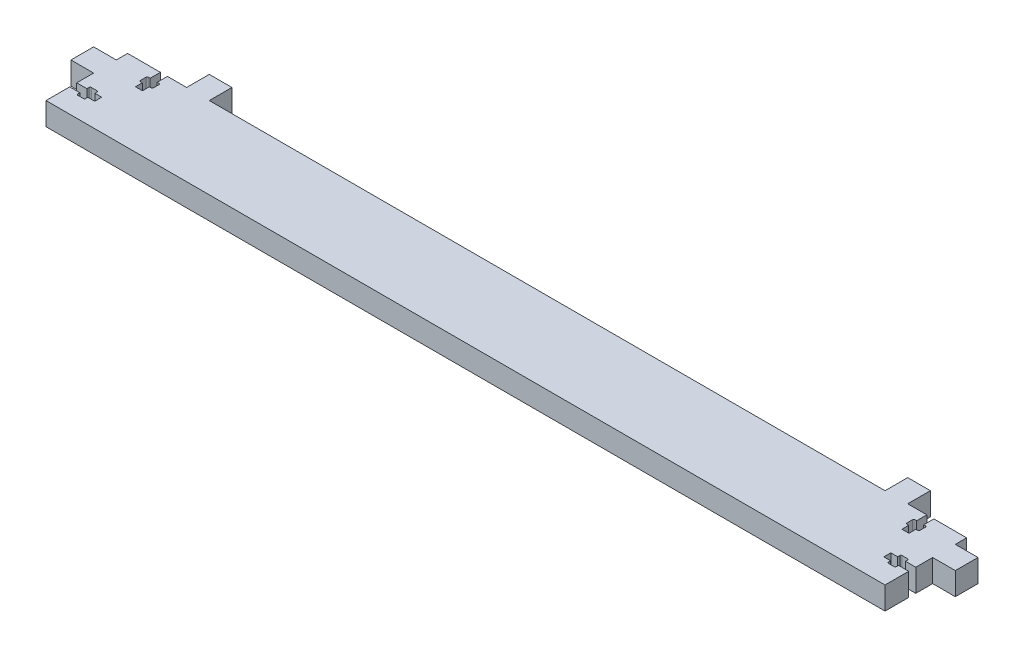
SolidWorks part; units mm, degrees
ref_plane "Front Plane" through (0, 0, 0) normal (0, 0, 1) x (1, 0, 0)
ref_plane "Top Plane" through (0, 0, 0) normal (0, 1, 0) x (1, 0, 0)
ref_plane "Right Plane" through (0, 0, 0) normal (1, 0, 0) x (0, 0, -1)
sketch "Sketch1" plane through (0, 0, 0) normal (0, 1, 0) x (1, 0, 0)
  line L0 (0, 18) -> (0, -18) construction
  line L1 (-185, 18) -> (0, 18)
  line L2 (-185, 18) -> (-185, 13)
  line L3 (-185, -18) -> (0, -18)
  line L4 (0, 18) -> (0, -18)
  line L5 (-185, 18) -> (0, 0) construction
  line L6 (-185, -18) -> (0, 0) construction
  line L7 (-185, 13) -> (-195, 13)
  line L8 (-195, 13) -> (-195, 3)
  line L9 (-195, 3) -> (-185, 3)
  line L10 (-185, 3) -> (-185, -18)
  point P0 (0, 0)
  dimension "D6" = 10
  dimension "D7" = 10
  dimension "D1" = 185
  dimension "D2" = 36
  dimension "D4" = 5
  dimension "D9" = 18
extrude "MainShape" add sketch "Sketch1" along normal blind 10 contours L2 L7 L8 L9 region at (-93.9423, 0, -0.1183)
sketch "Sketch2" plane through (0, 10, 0) normal (0, 1, 0) x (1, 0, 0)
  line L0 (-169, 18) -> (-169, 7) construction
  line L1 (-185, 18) -> (0, 18) construction
  line L2 (-170.55, 18) -> (-170.55, 13.5)
  line L3 (-170.55, 13.5) -> (-171.35, 13.5)
  line L4 (-171.85, 13) -> (-171.85, 10.5)
  line L5 (-171.35, 10) -> (-170.55, 10)
  line L6 (-170.55, 10) -> (-170.55, 7)
  line L7 (-170.55, 7) -> (-167.45, 7)
  line L8 (-185, 18) -> (-185, 13) construction
  line L9 (-170.55, 18) -> (-167.45, 18)
  line L10 (-167.45, 10) -> (-167.45, 7)
  line L11 (-166.65, 10) -> (-167.45, 10)
  line L12 (-166.15, 13) -> (-166.15, 10.5)
  line L13 (-167.45, 13.5) -> (-166.65, 13.5)
  line L14 (-167.45, 18) -> (-167.45, 13.5)
  line L16 (-185, -6) -> (-174, -6) construction
  line L50 (-185, 3) -> (-185, -18) construction
  line L51 (-174, -7.55) -> (-174, -4.45)
  line L52 (-174, -4.45) -> (-177, -4.45)
  line L53 (-177, -4.45) -> (-177, -3.5)
  line L54 (-177.5, -3) -> (-180, -3)
  line L55 (-180.5, -3.5) -> (-180.5, -4.45)
  line L56 (-180.5, -4.45) -> (-185, -4.45)
  line L57 (-185, -4.45) -> (-185, -7.55)
  line L58 (-195, 13) -> (-195, 3) construction
  line L59 (-180.5, -7.55) -> (-185, -7.55)
  line L60 (-180.5, -8.5) -> (-180.5, -7.55)
  line L61 (-177.5, -9) -> (-180, -9)
  line L62 (-177, -7.55) -> (-177, -8.5)
  line L63 (-174, -7.55) -> (-177, -7.55)
  arc A0 (-171.85, 10.5) -> (-171.35, 10) centre (-171.35, 10.5) ccw
  arc A1 (-171.35, 13.5) -> (-171.85, 13) centre (-171.35, 13) ccw
  arc A2 (-166.65, 13.5) -> (-166.15, 13) centre (-166.65, 13) cw
  arc A3 (-166.15, 10.5) -> (-166.65, 10) centre (-166.65, 10.5) cw
  arc A16 (-177, -3.5) -> (-177.5, -3) centre (-177.5, -3.5) ccw
  arc A17 (-180, -3) -> (-180.5, -3.5) centre (-180, -3.5) ccw
  arc A18 (-180, -9) -> (-180.5, -8.5) centre (-180, -8.5) cw
  arc A19 (-177, -8.5) -> (-177.5, -9) centre (-177.5, -8.5) cw
  point P14 (-171.85, 10)
  point P17 (-171.85, 13.5)
  point P28 (-166.15, 13.5)
  point P29 (-166.15, 10)
  point P34 (-195, 8)
  point P45 (-177, -3)
  point P48 (-180.5, -3)
  dimension "D8" = 0.5
  dimension "D16" = 0.5
  dimension "D1" = 11
  dimension "D2" = 1.55
  dimension "D3" = 1.55
  dimension "D4" = 8
  dimension "D5" = 2.85
  dimension "D6" = 3.5
  dimension "D7" = 16
  dimension "D9" = 11
  dimension "D10" = 8
  dimension "D11" = 3.5
  dimension "D12" = 3
  dimension "D13" = 1.55
  dimension "D14" = 1.55
  dimension "D15" = 14
extrude "ScrewSlots" cut sketch "Sketch2" against normal through all
mirror "Mirror1" about plane through (0, 0, 0) normal (1, 0, 0) of "ScrewSlots", "MainShape"
sketch "Sketch6" [suppressed] plane through (0, 10, 0) normal (0, 1, 0) x (1, 0, 0)
  line L0 (0, -18) -> (0, -48) construction
  line L2 (-185, -18) -> (185, -18) construction
  line L3 (90, -48) -> (-90, -48)
  line L4 (-90, -48) -> (-120, -18)
  line L5 (90, -48) -> (120, -18)
  line L6 (-120, -18) -> (120, -18)
  dimension "D1" = 135
  dimension "D2" = 30
  dimension "D3" = 90
extrude "Boss-Extrude1" [suppressed] add sketch "Sketch6" against normal through all
sketch "Sketch8" [suppressed] plane through (0, 10, 0) normal (0, 1, 0) x (1, 0, 0)
  line L0 (-71.5, 4.8833) -> (-77.5, 4.8833) construction
  line L1 (-77, -1.6167) -> (-72, -1.6167)
  line L2 (-78, -0.6167) -> (-78, 4.3833)
  line L3 (-77, 5.3833) -> (-72, 5.3833)
  line L4 (-71, -0.6167) -> (-71, 4.3833)
  line L5 (-78, -1.6167) -> (-71, 5.3833) construction
  line L6 (-78, 5.3833) -> (-71, -1.6167) construction
  line L7 (-71.5, -1.1167) -> (-71.5, 4.8833) construction
  circle A0 centre (-74.5, -34.7667) radius 6.5
  circle A1 centre (-74.5, -15.8167) radius 5.5
  arc A2 (-77, -1.6167) -> (-78, -0.6167) centre (-77, -0.6167) cw
  circle A3 centre (-74.5, -34.7667) radius 6 construction
  circle A4 centre (-74.5, -15.8167) radius 3.5 construction
  arc A5 (-72, -1.6167) -> (-71, -0.6167) centre (-72, -0.6167) ccw
  arc A6 (-72, 5.3833) -> (-71, 4.3833) centre (-72, 4.3833) cw
  arc A7 (-78, 4.3833) -> (-77, 5.3833) centre (-77, 4.3833) cw
  point P6 (-74.5, 1.8833)
  dimension "D1" = 0.5
  dimension "D2" = 2
  dimension "D3" = 0.5
  dimension "D5" = 1
  dimension "D4" = 0.5
extrude "Cut-Extrude2" [suppressed] cut sketch "Sketch8" against normal through all
sketch "Sketch7" [suppressed] plane through (0, 10, 0) normal (0, 1, 0) x (1, 0, 0)
  circle A0 centre (60.5, -43.0167) radius 1.45
  circle A1 centre (-84.5, -43.0167) radius 1.45
  circle A2 centre (-84.5, 6.4833) radius 1.45
  circle A3 centre (60.5, 6.4833) radius 1.45
  dimension "D1" = 2.9
  dimension "D2" = 2.9
  dimension "D3" = 2.9
  dimension "D4" = 2.9
extrude "Cut-Extrude1" [suppressed] cut sketch "Sketch7" against normal through all
sketch "Sketch9" [suppressed] plane through (0, 10, 0) normal (0, 1, 0) x (1, 0, 0)
  line L0 (0, 7.2333) -> (0, -32.7667) construction
  line L1 (48.5, 7.2333) -> (-48.5, 7.2333) construction
  line L2 (-48.5, -32.7667) -> (48.5, -32.7667) construction
  line L3 (-48.5, -12.7667) -> (48.5, -12.7667) construction
  line L4 (-48.5, 7.2333) -> (-48.5, -32.7667) construction
  line L5 (48.5, -32.7667) -> (48.5, 7.2333) construction
  line L7 (-49, -33.2667) -> (49, -33.2667)
  line L8 (-49, -33.2667) -> (-49, 7.7333)
  line L9 (-49, 7.7333) -> (49, 7.7333)
  line L10 (49, -33.2667) -> (49, 7.7333)
  line L11 (-49, -33.2667) -> (49, 7.7333) construction
  line L12 (-49, 7.7333) -> (49, -33.2667) construction
  point P12 (0, -12.7667)
  dimension "D1" = 0.5
  dimension "D2" = 0.5
extrude "Cut-Extrude3" [suppressed] cut sketch "Sketch9" against normal through all and the other way through all
sketch "Sketch10" [suppressed] plane through (0, 10, 0) normal (0, 1, 0) x (1, 0, 0)
  line L0 (20, -39.2667) -> (20, -40.7667) construction
  line L1 (40, -39.2667) -> (0, -39.2667) construction
  line L2 (0, -40.7667) -> (40, -40.7667) construction
  line L3 (0, -40.0167) -> (40, -40.0167) construction
  line L4 (0, -39.2667) -> (0, -40.7667) construction
  line L5 (40, -40.7667) -> (40, -39.2667) construction
  line L7 (-0.2, -40.9667) -> (40.2, -40.9667)
  line L8 (-0.2, -40.9667) -> (-0.2, -39.0667)
  line L9 (-0.2, -39.0667) -> (40.2, -39.0667)
  line L10 (40.2, -40.9667) -> (40.2, -39.0667)
  line L11 (-0.2, -40.9667) -> (40.2, -39.0667) construction
  line L12 (-0.2, -39.0667) -> (40.2, -40.9667) construction
  point P12 (20, -40.0167)
  dimension "D1" = 0.2
  dimension "D2" = 0.2
extrude "Cut-Extrude4" [suppressed] cut sketch "Sketch10" against normal through all
sketch "Sketch12" [suppressed] plane through (0, 0, 0) normal (0, -1, 0) x (-1, 0, 0)
  line L1 (81.4, -9.8167) -> (67.6, -9.8167)
  line L2 (81.4, -9.8167) -> (81.4, -21.8167)
  line L3 (81.4, -21.8167) -> (67.6, -21.8167)
  line L4 (67.6, -9.8167) -> (67.6, -21.8167)
  line L5 (81.4, -9.8167) -> (67.6, -21.8167) construction
  line L6 (81.4, -21.8167) -> (67.6, -9.8167) construction
  point P0 (74.5, -15.8167)
  dimension "D1" = 13.8
  dimension "D2" = 12
extrude "PotentiometerAdjustment" [suppressed] cut sketch "Sketch12" against normal through all
sketch "Sketch11" plane through (0, 0, 0) normal (0, -1, 0) x (1, 0, 0)
  line L1 (-149, -2) -> (-167, -2)
  line L2 (-147, 0) -> (-147, 7)
  line L3 (-149, 9) -> (-167, 9)
  line L4 (-169, 0) -> (-169, 7)
  line L5 (-147, -2) -> (-169, 9) construction
  line L6 (-147, 9) -> (-169, -2) construction
  line L7 (170.55, -7) -> (167.45, -7) construction
  line L8 (-174, 7.55) -> (-174, 4.45) construction
  arc A0 (-147, 7) -> (-149, 9) centre (-149, 7) ccw
  arc A1 (-167, 9) -> (-169, 7) centre (-167, 7) ccw
  arc A2 (-167, -2) -> (-169, 0) centre (-167, 0) cw
  arc A3 (-149, -2) -> (-147, 0) centre (-149, 0) ccw
  point P0 (-158, 3.5)
  dimension "D3" = 2
  dimension "D1" = 22
  dimension "D2" = 11
  dimension "D4" = 5
  dimension "D5" = 5
extrude "LCDCableCutout" [suppressed] cut sketch "Sketch11" against normal through all
sketch "Sketch13" plane through (0, 10, 0) normal (0, 1, 0) x (1, 0, 0)
  line L0 (0, 18) -> (0, -18) construction
  line L1 (-167.45, 18) -> (167.45, 18) construction
  line L2 (-185, -18) -> (185, -18) construction
  line L3 (120, 18) -> (-120, 18) construction
  line L4 (120, 8) -> (-120, 8)
  line L5 (120, 28) -> (-120, 28)
  arc A0 (120, 8) -> (120, 28) centre (120, 18) ccw
  arc A1 (-120, 28) -> (-120, 8) centre (-120, 18) ccw
  point P8 (0, 18)
  dimension "D2" = 120
  dimension "D1" = 10
extrude "Cut-Extrude5" [suppressed] cut sketch "Sketch13" against normal through all
sketch "Sketch14" plane through (0, 10, 0) normal (0, 1, 0) x (1, 0, 0)
  line L1 (-167.45, 18) -> (167.45, 18) construction
  line L3 (-154, 18) -> (-154, 28) construction
  line L4 (-159, 18) -> (-149, 18)
  line L5 (-159, 18) -> (-159, 28)
  line L6 (-159, 28) -> (-149, 28)
  line L7 (-149, 18) -> (-149, 28)
  line L8 (-170.55, 7) -> (-167.45, 7) construction
  line L9 (154, 18) -> (154, 28) construction
  line L10 (149, 18) -> (149, 28)
  line L11 (159, 28) -> (149, 28)
  line L12 (159, 18) -> (159, 28)
  line L13 (159, 18) -> (149, 18)
  point P12 (-169, 7)
  dimension "D1" = 10
  dimension "D2" = 10
  dimension "D3" = 15
extrude "Boss-Extrude3" add sketch "Sketch14" against normal through all
equation "\"Y-ROD-SPACING\"=75"
equation "\"Y-BED-OFFSET\"=2"
equation "\"Y-BED-ROD-INSET\"=3.5"
equation "\"T-SLOT-NUT-FILLET-RADIUS\"=0.5"
equation "\"T-SLOT-SCREW-SHAFT-RADIUS\"=1.55"
equation "\"T-SLOT-SCREW-SHAFT-CUTOUT-LENGTH\"=11.0"
equation "\"T-SLOT-NUT-DEPTH\"=3.5"
equation "\"T-SLOT-NUT-WIDTH\"=2.85"
equation "\"T-SLOT-NUT-END-DISTANCE\"=8"
equation "\"ACRYLIC-TAB-CUTOUT-SIZE\"=\"ACRYLIC-THICKNESS\"+\"ACRYLIC-TAB-TOLERANCE\"*2"
equation "\"ACRYLIC-M3-HOLE\"=2.9"
equation "\"SMOOTHROD-CAP-SCREW-DISTANCE\"=20"
equation "\"D2@Sketch2\"=\"T-SLOT-SCREW-SHAFT-RADIUS\""
equation "\"D1@Sketch2\"=\"T-SLOT-SCREW-SHAFT-CUTOUT-LENGTH\""
equation "\"D6@Sketch2\"=\"T-SLOT-NUT-DEPTH\""
equation "\"D5@Sketch2\"=\"T-SLOT-NUT-WIDTH\""
equation "\"D3@Sketch2\"=\"T-SLOT-SCREW-SHAFT-RADIUS\""
equation "\"D8@Sketch2\"=\"T-SLOT-NUT-FILLET-RADIUS\""
equation "\"D4@Sketch2\"=\"T-SLOT-NUT-END-DISTANCE\""
equation "\"D11@Sketch2\"=\"T-SLOT-NUT-DEPTH\""
equation "\"D10@Sketch2\"=\"T-SLOT-NUT-END-DISTANCE\""
equation "\"D13@Sketch2\"=\"T-SLOT-SCREW-SHAFT-RADIUS\""
equation "\"D14@Sketch2\"=\"T-SLOT-SCREW-SHAFT-RADIUS\""
equation "\"D16@Sketch2\"=\"T-SLOT-NUT-FILLET-RADIUS\""
equation "\"D9@Sketch2\"=\"T-SLOT-SCREW-SHAFT-CUTOUT-LENGTH\""
equation "\"ACRYLIC-TAB-WIDTH\"=\"ACRYLIC-THICKNESS\""
equation "\"D6@Sketch1\"=\"ACRYLIC-TAB-WIDTH\""
equation "\"D7@Sketch1\"=\"ACRYLIC-TAB-WIDTH\""
equation "\"FRAME-WIDTH-INNER\"=370"
equation "\"D1@Sketch1\"=\"FRAME-WIDTH-INNER\"/2"
equation "\"X-ROD-SPACING\"=45"
equation "\"Z-ROD-SPACING\"=17.5"
equation "\"ACRYLIC-THICKNESS\"=10"
equation "\"ACRYLIC-THICKNESS2\"=4.5"
equation "\"NEMA17-HOLE-SPACING\"=31"
equation "\"NEMA17-CENTRAL-CUTOUT\"=22.5"
equation "\"Z-BRACKET-REACH\"=55"
equation "\"TOP-BRACKET-SPACING\"=40"
equation "\"SMOOTHROD-X-LENGTH\"=350"
equation "\"SMOOTHROD-Y-LENGTH\"=350"
equation "\"SMOOTHROD-Z-LENGTH\"=350"
equation "\"SMOOTHROD-TIGHTENING-HEADROOM\"=.25"
equation "\"LEADSCREW-Z-LENGTH\"=300"
equation "\"SCREW-LENGTH-FRAME\"=\"ACRYLIC-THICKNESS\" + 10"
equation "\"SCREW-HEAD-RADIUS\"=6"
equation "\"PRINTED-X-SMOOTHROD-DIAMETER\"=9.0"
equation "\"PRINTED-X-SMOOTHROD-CUTOUT\"=10"
equation "\"PRINTED-X-BASE-HEIGHT\"=10"
equation "\"PRINTED-LM8UU-CUTOUT-SIZE\"=15.5"
equation "\"PRINTED-LM8UU-CUTOUT-LENGTH\"=24.5"
equation "\"PRINTED-X-IDLER-HEIGHT\"=16"
equation "\"PSU-MOUNTING-WIDTH\"=95"
equation "\"PSU-MOUNTING-HEIGHT\"=177"
equation "\"D1@MainShape\"=\"ACRYLIC-THICKNESS\""
equation "\"Y-BELT-TO-ROD-DISTANCE\"=20"
equation "\"SPOOL-HOLDER-ROD-SPACING\"=150"
equation "\"Z-ROD-INSET\"=16"
equation "\"D7@Sketch2\"=\"Z-ROD-INSET\""
equation "\"D1@Sketch7\"=\"ACRYLIC-M3-HOLE\""
equation "\"D2@Sketch7\"=\"ACRYLIC-M3-HOLE\""
equation "\"D3@Sketch7\"=\"ACRYLIC-M3-HOLE\""
equation "\"D4@Sketch7\"=\"ACRYLIC-M3-HOLE\""
equation "\"Y-BED-SCREW-SPACING\"=209"
equation "\"Y-BED-SCREW-CUTOUT-SLOT-HEIGHT\"=2"
equation "\"ACRYLIC-TAB-TOLERANCE\"=-.05"
equation "\"SCREW-LENGTH-MOTOR\"=\"ACRYLIC-THICKNESS\" + 5"
equation "\"SCREW-LENGTH-EXTRUDER\"=28"
equation "\"PRINTED-M3-HOLE\"=3.5"
equation "\"PRINTED-M3-NUT-AF\"=6.25"
equation "\"ACRYLIC-X-CARRIAGE-WIDTH\"=55"
equation "\"ACRYLIC-X-CARRIAGE-HEIGHT\"=75"
equation "\"ACRYLIC-X-CARRIAGE-LM8UU-CUTOUT-WIDTH\"=24.25"
equation "\"ACRYLIC-X-CARRIAGE-LM8UU-CUTOUT-HEIGHT\"=11.0"
equation "\"ACRYLIC-X-CARRIAGE-SCREW-SPACING-X\"=15"
equation "\"ACRYLIC-X-CARRIAGE-SCREW-SPACING-Y\"=33"
equation "\"ACRYLIC-X-CARRIAGE-CENTER-TAB-SPACING\"=14"
equation "\"ACRYLIC-X-CARRIAGE-EXTRUDER-OFFSET\"=26"
equation "\"ACRYLIC-X-CARRIAGE-EXTRUDER-ANGLE\"=90"
equation "\"ACRYLIC-X-CARRIAGE-EXTRUDER-SHELF-DEPTH\"=\"ACRYLIC-X-CARRIAGE-EXTRUDER-OFFSET\" + 28"
equation "\"ACRYLIC-X-CARRIAGE-EXTRUDER-BRACE-SPACING\"=23"
equation "\"ACRYLIC-X-CARRIAGE-EXTRUDER-BRACE-TAB-OFFSET\"=20"
equation "\"ACRYLIC-X-CARRIAGE-EXTRUDER-BRACE-HEIGHT\"=35"
equation "\"ACRYLIC-X-CARRIAGE-EXTRUDER-BRACE-SCREW-SPACING\"=22"
equation "\"ACRYLIC-X-CARRIAGE-DUAL-WIDTH-MULTIPLIER\"=1.65"
equation "\"ACRYLIC-X-CARRIAGE-DUAL-HOTEND-SPACING\"=42"
equation "\"ACRYLIC-X-CARRIAGE-DUAL-WIDTH\"=75"
equation "\"ACRYLIC-X-CARRIAGE-DUAL-HOTEND-SEPARATION\"=36"
equation "\"ACRYLIC-X-CARRIAGE-DUAL-MOUNT-PLATE-DEPTH\"=75"
equation "\"ACRYLIC-X-CARRIAGE-DUAL-MOUNT-BRACE-WIDTH\"=33"
equation "\"ACRYLIC-X-CARRIAGE-DUAL-MOUNT-SCREW-WIDTH\"=40"
equation "\"BLOWER-FAN-WIDTH\"=15"
equation "\"D1@Sketch14\"=\"ACRYLIC-TAB-WIDTH\""
equation "\"D2@Sketch14\"=\"ACRYLIC-THICKNESS\""
